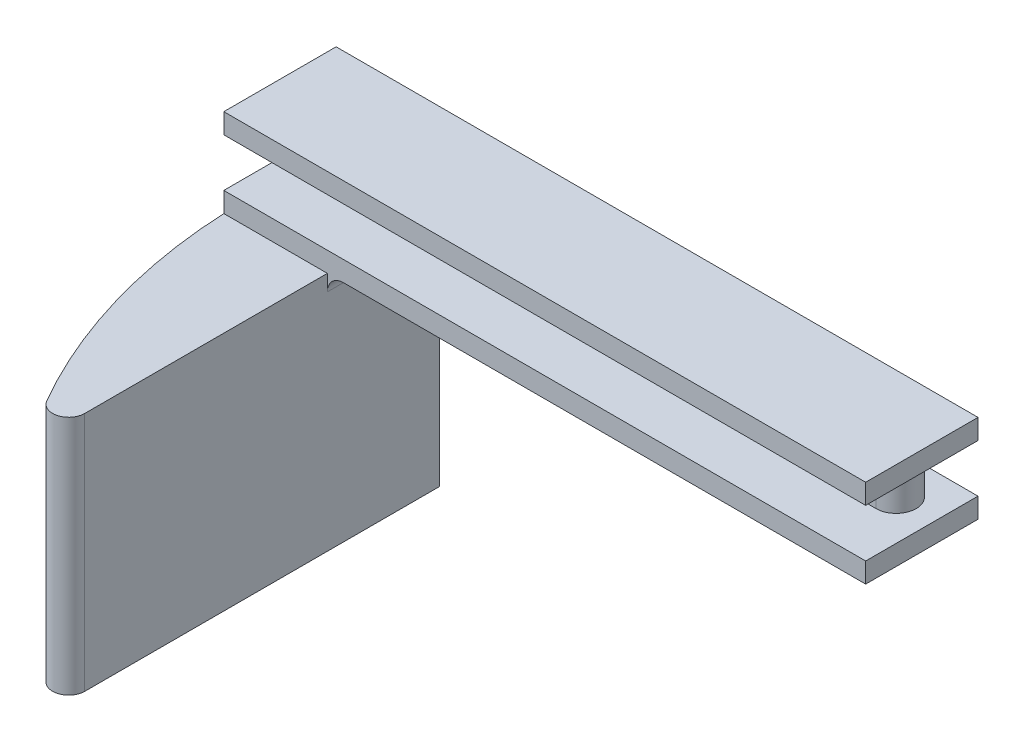
SolidWorks part; units mm, degrees
ref_plane "Front Plane" through (0, 0, 0) normal (0, 0, 1) x (1, 0, 0)
ref_plane "Top Plane" through (0, 0, 0) normal (0, 1, 0) x (1, 0, 0)
ref_plane "Right Plane" through (0, 0, 0) normal (1, 0, 0) x (0, 0, -1)
sketch "Sketch2" plane through (0, 0, 0) normal (0, 1, 0) x (1, 0, 0)
  line L1 (0, 0) -> (101.6, 0)
  line L2 (0, 0) -> (0, 17.78)
  line L3 (0, 17.78) -> (101.6, 17.78)
  line L4 (101.6, 0) -> (101.6, 17.78)
  dimension "D1" = 17.78
  dimension "D2" = 101.6
extrude "Boss-Extrude1" add sketch "Sketch2" along normal blind 3.175
sketch "Sketch3" plane through (0, 0, 0) normal (0, -1, 0) x (1, 0, 0)
  line L0 (95.25, -11.176) -> (6.35, -11.176) construction
  line L1 (95.25, -14.351) -> (6.35, -14.351)
  line L2 (95.25, -8.001) -> (6.35, -8.001)
  line L3 (0, 0) -> (101.6, 0) construction
  line L4 (0, -17.78) -> (0, 0) construction
  arc A0 (95.25, -14.351) -> (95.25, -8.001) centre (95.25, -11.176) ccw
  arc A1 (6.35, -8.001) -> (6.35, -14.351) centre (6.35, -11.176) ccw
  point P2 (50.8, -11.176)
  dimension "D1" = 88.9
  dimension "D2" = 11.176
  dimension "D3" = 6.35
  dimension "D4" = 6.35
extrude "Boss-Extrude2" add sketch "Sketch3" along normal blind 7.62 contours L2 A1 L1 A0
ref_plane "Plane1" through (0, -3.81, 0) normal (0, -1, 0) x (-1, 0, 0)
mirror "Mirror1" about plane through (0, -3.81, 0) normal (0, -1, 0) of "Boss-Extrude1"
sketch "Sketch4" plane through (0, -10.795, 0) normal (0, -1, 0) x (1, 0, 0)
  line L0 (0, 0) -> (101.6, 0) construction
  line L1 (0, -17.78) -> (16.3938, -17.78)
  line L2 (0, -17.78) -> (0, 0)
  line L4 (16.3938, -17.78) -> (16.3938, 0)
  line L5 (16.3938, 0) -> (16.3938, 47.009)
  arc A0 (0, 0) -> (16.3938, 47.009) centre (87.5, -4.1516) cw
extrude "Boss-Extrude3" add sketch "Sketch4" along normal blind 38.1
fillet "Fillet1" radius 2.54 1 edges at (16.3938, -10.795, -8.89)
fillet "Fillet2" radius 2.54 1 edges at (16.3938, -29.845, 47.009)
